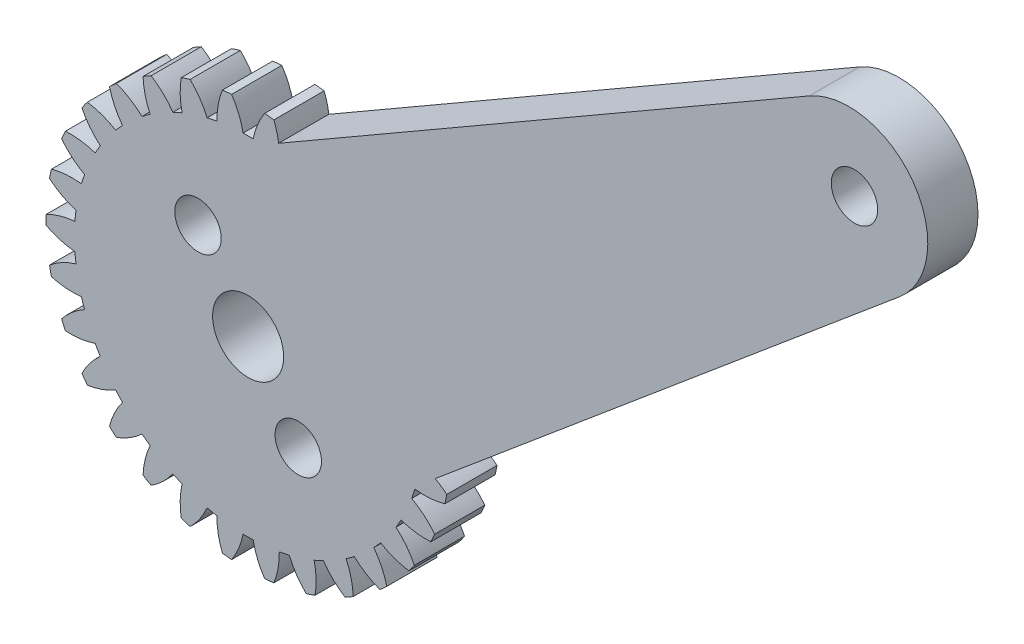
SolidWorks part; units mm, degrees
ref_plane "Front Plane" through (0, 0, 0) normal (0, 0, 1) x (1, 0, 0)
ref_plane "Top Plane" through (0, 0, 0) normal (0, 1, 0) x (1, 0, 0)
ref_plane "Right Plane" through (0, 0, 0) normal (1, 0, 0) x (0, 0, -1)
sketch "Sketch1" plane through (0, 0, 0) normal (0, 0, 1) x (1, 0, 0)
  circle A0 centre (0, 0) radius 12.8
  dimension "D1" = 25.6
extrude "Boss-Extrude1" add sketch "Sketch1" along normal blind 3.18
sketch "Sketch2" plane through (0, 0, 3.18) normal (0, 0, 1) x (1, 0, 0)
  line L0 (0, 0) -> (0, 12.8) construction
  line L1 (0, 0) -> (-1.338, 12.7299) construction
  line L2 (-0.6243, 11.9838) -> (-1.2526, 11.9177) construction
  circle A0 centre (0, 0) radius 11 construction
  circle A1 centre (0, 0) radius 11.2763 construction
  circle A2 centre (0, 0) radius 12 construction
  circle A5 centre (0, 0) radius 12.8 construction
  arc A6 (-0.321, 10.9953) -> (0.321, 10.9953) centre (0, 0) cw
  arc A7 (-1.0443, 12.7573) -> (1.0443, 12.7573) centre (0, 0) cw
  arc A8 (-1.0443, 12.7573) -> (-0.321, 10.9953) centre (-5.0349, 10.0899) cw
  arc A9 (0.321, 10.9953) -> (1.0443, 12.7573) centre (5.0349, 10.0899) cw
  dimension "D1" = 22
  dimension "D2" = 22.5526
  dimension "D3" = 24
  dimension "D5" = 4.8
  dimension "D6" = 4.8
  dimension "D4" = 6
  dimension "D7" = 0.6283
extrude "Cut-Extrude1" cut sketch "Sketch2" against normal through all
pattern_circular "CirPattern1" count 30 over 360 about axis through (0, 0, 3.18) along (0, 0, 1) of face at (-0.6385, 11.8944, 1.59) of face at (0, 10.9977, 1.59) of face at (0.6385, 11.8944, 1.59)
ref_axis "Axis1" through (0, 0, 0) along (0, 0, 1)
sketch "Sketch4" plane through (0, 0, 3.18) normal (0, 0, 1) x (1, 0, 0)
  circle A1 centre (0, 0) radius 2.25
  dimension "D1" = 4.5
extrude "Cut-Extrude3" cut sketch "Sketch4" against normal through all
sketch "Sketch6" plane through (0, 0, 0) normal (0, 0, -1) x (-1, 0, 0)
  line L0 (-38.0364, 26.6334) -> (0, 0) construction
  line L1 (-35.5364, 30.9635) -> (-0.8954, 10.9635)
  line L3 (-41.2503, 22.8031) -> (-10.6086, -2.9084)
  line L5 (0, 0) -> (0, -9.5005) construction
  arc A0 (-41.2503, 22.8031) -> (-35.5364, 30.9635) centre (-38.0364, 26.6334) cw
  arc A3 (-0.8954, 10.9635) -> (-10.6086, -2.9084) centre (0, 0) ccw
  arc A4 (-10.358, 3.7031) -> (-10.5564, 3.0924) centre (0, 0) ccw construction
  dimension "D1" = 10
  dimension "D2" = 40
  dimension "D3" = 125
  dimension "D4" = 5
extrude "Boss-Extrude6" add sketch "Sketch6" against normal blind 3.18
sketch "Sketch8" plane through (0, 0, 3.18) normal (0, 0, 1) x (1, 0, 0)
  line L0 (0, 0) -> (-3.1735, 4.5265) construction
  line L1 (0, 0) -> (3.1735, -4.5265) construction
  line L2 (0, 0) -> (0, 4.9284) construction
  circle A0 centre (-3.1735, 4.5265) radius 1.47
  circle A1 centre (3.1735, -4.5265) radius 1.47
  dimension "D1" = 2.94
  dimension "D2" = 2.94
  dimension "D3" = 5.5281
  dimension "D4" = 180
  dimension "D5" = 144.966
  dimension "D6" = 5.5281
  dimension "D7" = 11
  dimension "D8" = 11
extrude "Cut-Extrude4" cut sketch "Sketch8" against normal through all
sketch "Sketch9" plane through (0, 0, 0) normal (0, 0, -1) x (-1, 0, 0)
  line L0 (-41.2503, 22.8031) -> (-35.5364, 30.9635) construction
  circle A0 centre (-38.3934, 26.8833) radius 1.47
  dimension "D1" = 2.94
extrude "Cut-Extrude5" cut sketch "Sketch9" against normal through all
equation "\"module\"= .8"
equation "\"teeth\"= 30"
equation "\"pressureAngle\"= 20deg"
equation "\"gearThickness\"=3.18"
equation "\"addendumFactor\"= 1"
equation "\"dedendumFactor\"= 1.25"
equation "\"pitch\"= 1 / \"module\""
equation "\"pitchDiameter\"= \"teeth\" / \"pitch\""
equation "\"addendum\"= \"addendumFactor\" / \"pitch\""
equation "\"dedendum\"= \"dedendumFactor\" / \"pitch\""
equation "\"D1@Sketch1\"=\"pitchDiameter\" + 2 * \"addendum\""
equation "\"D1@Boss-Extrude1\"=\"gearThickness\""
equation "\"D1@Sketch2\"=\"pitchDiameter\" - 2 * \"dedendum\""
equation "\"D2@Sketch2\"=\"pitchDiameter\" * cos(\"pressureAngle\")"
equation "\"D3@Sketch2\"=\"pitchDiameter\""
equation "\"D4@Sketch2\"=180/\"teeth\""
equation "\"D5@Sketch2\"=\"pitchDiameter\"/5"
equation "\"D6@Sketch2\"=\"pitchDiameter\"/5"
equation "\"D7@Sketch2\"= PI / 2 / \"pitch\"/2"
equation "\"D1@CirPattern1\"=\"teeth\""
